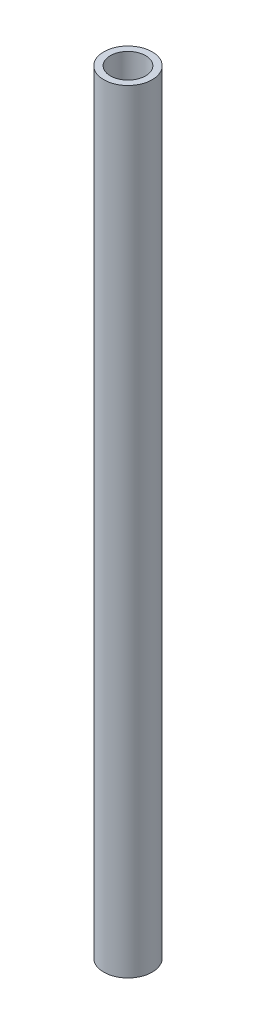
SolidWorks part; units mm, degrees
ref_plane "Front Plane" through (0, 0, 0) normal (0, 0, 1) x (1, 0, 0)
ref_plane "Top Plane" through (0, 0, 0) normal (0, 1, 0) x (1, 0, 0)
ref_plane "Right Plane" through (0, 0, 0) normal (1, 0, 0) x (0, 0, -1)
sketch "Sketch1" plane through (0, 0, 0) normal (0, 1, 0) x (1, 0, 0)
  circle A0 centre (0, 0) radius 12.1539
  circle A1 centre (0, 0) radius 16.7005
  dimension "D1" = 33.401
  dimension ".658" = 24.3078
extrude "Boss-Extrude1" add sketch "Sketch1" along normal mid plane 533.4
